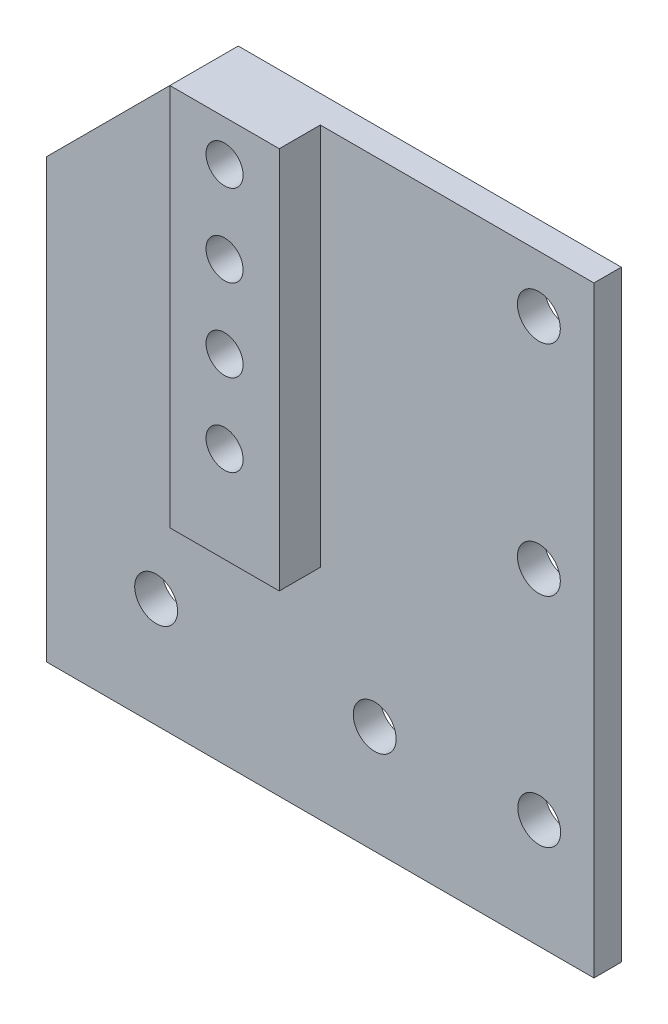
SolidWorks part; units mm, degrees
ref_plane "Front Plane" through (0, 0, 0) normal (0, 0, 1) x (1, 0, 0)
ref_plane "Top Plane" through (0, 0, 0) normal (0, 1, 0) x (1, 0, 0)
ref_plane "Right Plane" through (0, 0, 0) normal (1, 0, 0) x (0, 0, -1)
sketch "Sketch1" plane through (0, 0, 0) normal (0, 0, 1) x (1, 0, 0)
  line L15 (-266.7, -12.7) -> (-266.7, 57.15)
  line L16 (-266.7, 609.6) -> (-266.7, -16.7024) construction
  line L18 (-279.4, -12.7) -> (-266.7, -12.7)
  line L19 (-279.4, -12.7) -> (-330.2, -12.7)
  line L20 (-330.2, -12.7) -> (-330.2, 12.7)
  line L21 (-330.2, 12.7) -> (-330.2, 38.1)
  line L22 (-311.15, 57.15) -> (-330.2, 38.1)
  line L23 (-279.4, 57.15) -> (-311.15, 57.15)
  line L24 (-266.7, 57.15) -> (-279.4, 57.15)
  dimension "D1" = 69.85
  dimension "D2" = 50.8
  dimension "D3" = 12.7
extrude "Boss-Extrude1" add sketch "Sketch1" along normal blind 3.175
sketch "Sketch2" plane through (0, 0, 3.175) normal (0, 0, 1) x (1, 0, 0)
  line L0 (-787.4, 12.7) -> (-279.4, 12.7) construction
  line L1 (-787.4, -12.7) -> (-279.4, -12.7) construction
  line L10 (-273.05, 25.4) -> (-273.0882, 50.7989) construction
  line L11 (-273.05, 0) -> (-273.05, 25.4) construction
  line L12 (-273.05, -12.7) -> (-273.05, 0) construction
  line L13 (-279.4, -12.7) -> (-266.7, -12.7) construction
  line L14 (-330.2, 0) -> (-317.5, 0) construction
  line L15 (-317.5, 0) -> (-292.1, 0) construction
  line L16 (-330.2, -12.7) -> (-330.2, 12.7) construction
  point P0 (0, 0)
  dimension "D1" = 12.7
  dimension "D2" = 25.4
  dimension "D3" = 25.4
  dimension "D4" = 12.7
  dimension "D5" = 25.3989
  dimension "D6" = 12.7
  dimension "D7" = 19.05
hole_wizard "#10 Clearance Hole1" positions "Sketch3" profile "Sketch4" hole size "#10" standard "ANSI Inch" end condition through all
sketch "Sketch3" plane through (0, 0, 3.175) normal (0, 0, 1) x (1, 0, 0)
  point P30 (-273.0882, 50.5983)
  point P33 (-273.0882, 25.2365)
  point P36 (-273.05, 0)
  point P41 (-317.5, 0)
  point P44 (-292.1382, -0.1635)
sketch "Sketch4" plane through (-273.0882, 50.5983, 3.175) normal (1, 0, 0) x (0, -1, 0)
  line L0 (0, 0) -> (0, 3.175)
  line L1 (0, 3.175) -> (2.4892, 3.175)
  line L2 (2.4892, 3.175) -> (2.4892, 0)
  line L5 (2.4892, 0) -> (0, 0)
  line L11 (0, -6.35) -> (0, 107.95) construction
  dimension "Thru Hole Dia." = 4.9784
  dimension "Thru Hole Depth" = 3.175
sketch "Sketch5" plane through (0, 0, 3.175) normal (0, 0, 1) x (1, 0, 0)
  line L0 (-311.15, 12.7) -> (-298.45, 12.7)
  line L9 (-311.15, 57.15) -> (-311.15, 12.7)
  line L10 (-298.45, 12.7) -> (-298.45, 57.15)
  line L13 (-266.7, 57.15) -> (-311.15, 57.15) construction
  line L17 (-298.45, 57.15) -> (-311.15, 57.15)
  dimension "D1" = 44.45
  dimension "D2" = 12.7
extrude "Boss-Extrude2" add sketch "Sketch5" along normal blind 4.7625
sketch "Sketch6" plane through (0, 0, 7.9375) normal (0, 0, 1) x (1, 0, 0)
  line L0 (-304.8, 57.15) -> (-304.8, 52.3875) construction
  line L1 (-304.8, 52.3875) -> (-304.8, 42.8625) construction
  line L2 (-304.8, 42.8625) -> (-304.8, 33.3375) construction
  line L4 (-304.8, 33.3375) -> (-304.8, 23.8125) construction
  line L5 (-298.45, 57.15) -> (-311.15, 57.15) construction
  dimension "D1" = 9.525
  dimension "D2" = 4.7625
  dimension "D3" = 9.525
  dimension "D4" = 9.525
hole_wizard "#8 Clearance Hole1" positions "Sketch7" profile "Sketch8" hole size "#8" standard "ANSI Inch" end condition through all
sketch "Sketch7" plane through (0, 0, 7.9375) normal (0, 0, 1) x (1, 0, 0)
  point P0 (-304.8, 42.8625)
  point P3 (-304.8, 52.3875)
  point P7 (-304.8, 33.3375)
  point P10 (-304.8, 23.8125)
sketch "Sketch8" plane through (-304.8, 42.8625, 7.9375) normal (1, 0, 0) x (0, -1, 0)
  line L0 (0, 0) -> (0, 7.9375)
  line L1 (0, 7.9375) -> (2.1526, 7.9375)
  line L2 (2.1526, 7.9375) -> (2.1526, 0)
  line L5 (2.1526, 0) -> (0, 0)
  line L11 (0, -6.35) -> (0, 107.95) construction
  dimension "Thru Hole Dia." = 4.3053
  dimension "Thru Hole Depth" = 7.9375
